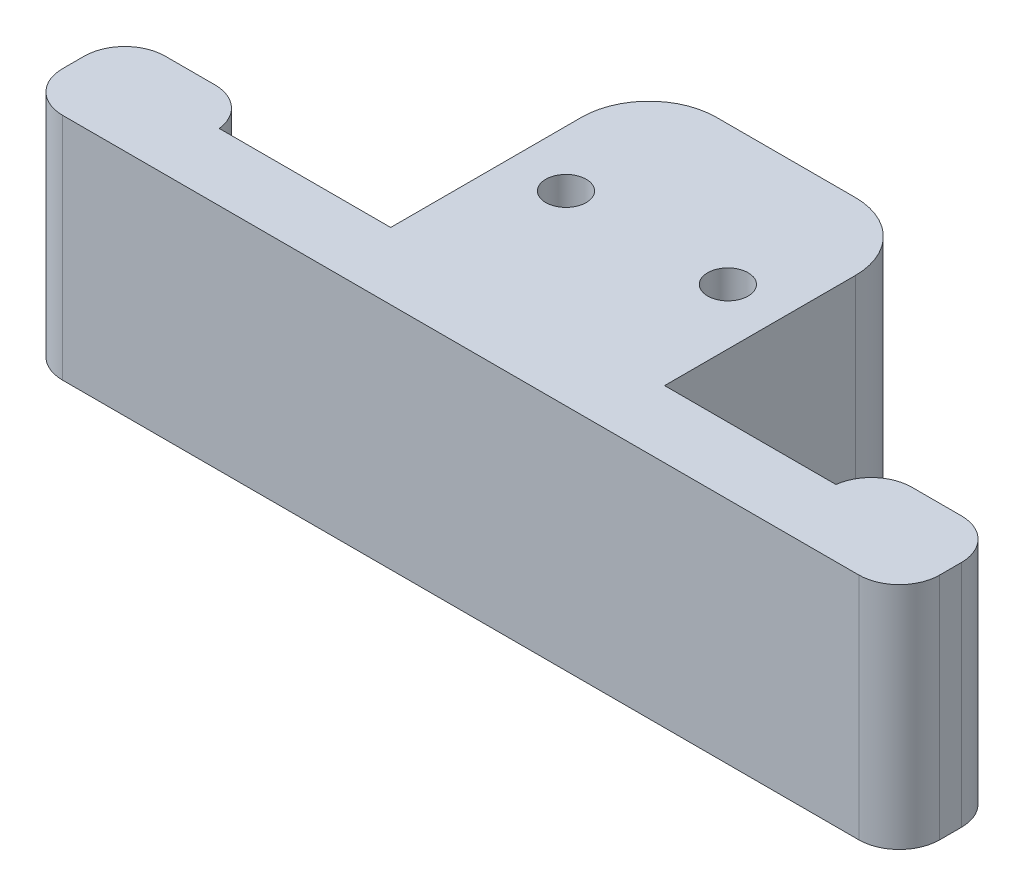
SolidWorks part; units mm, degrees
material "ABS"
ref_plane "Спереди" through (0, 0, 0) normal (0, 0, 1) x (1, 0, 0)
ref_plane "Сверху" through (0, 0, 0) normal (0, 1, 0) x (1, 0, 0)
ref_plane "Справа" through (0, 0, 0) normal (1, 0, 0) x (0, 0, -1)
sketch "Sketch1" plane through (0, 0, 0) normal (0, 1, 0) x (1, 0, 0)
  line L0 (0, 0) -> (-6, 0) construction
  line L2 (-32.5, -13.8) -> (32.5, -13.8)
  line L3 (32.5, -13.8) -> (32.5, -6.2)
  line L4 (10.15, -6.2) -> (10.15, 10.3)
  line L5 (10.15, 10.3) -> (-10.15, 10.3)
  line L6 (-10.15, 10.3) -> (-10.15, -8.84)
  line L7 (0, 0) -> (6, 0) construction
  line L8 (32.5, -6.2) -> (22.85, -6.2)
  line L11 (22.85, -6.2) -> (22.85, -8.84)
  line L12 (22.85, -8.84) -> (10.15, -8.84)
  line L13 (10.15, -8.84) -> (10.15, -6.2)
  line L14 (-10.15, -8.84) -> (-22.85, -8.84)
  line L15 (-22.85, -8.84) -> (-22.85, -6.2)
  line L16 (-22.85, -6.2) -> (-32.5, -6.2)
  line L17 (-32.5, -6.2) -> (-32.5, -13.8)
  circle A0 centre (-6, 0) radius 1.5
  circle A1 centre (6, 0) radius 1.5
  point P0 (0, 0)
  dimension "D4" = 3
  dimension "D3" = 12
extrude "Boss-Extrude1" add sketch "Sketch1" along normal blind 17
sketch "Sketch2" plane through (0, 0, 0) normal (0, -1, 0) x (1, 0, 0)
  circle A0 centre (-3.1, 10) radius 1
  circle A1 centre (-29.9, 10) radius 1
  circle A2 centre (3.1, 10) radius 1
  circle A3 centre (29.9, 10) radius 1
  circle A4 centre (3.1, 10) radius 1 construction
  circle A5 centre (-3.1, 10) radius 1 construction
  circle A6 centre (-29.9, 10) radius 1 construction
  circle A7 centre (29.9, 10) radius 1 construction
extrude "Cut-Extrude1" cut sketch "Sketch2" against normal blind 12
fillet "Fillet2" radius 5 2 edges at (10.15, 8.5, -10.3) (-10.15, 8.5, -10.3)
fillet "Fillet3" radius 3 6 edges at (-32.5, 8.5, 13.8) (32.5, 8.5, 13.8) (32.5, 8.5, 6.2) (22.85, 8.5, 6.2) (-22.85, 8.5, 6.2) (-32.5, 8.5, 6.2)
